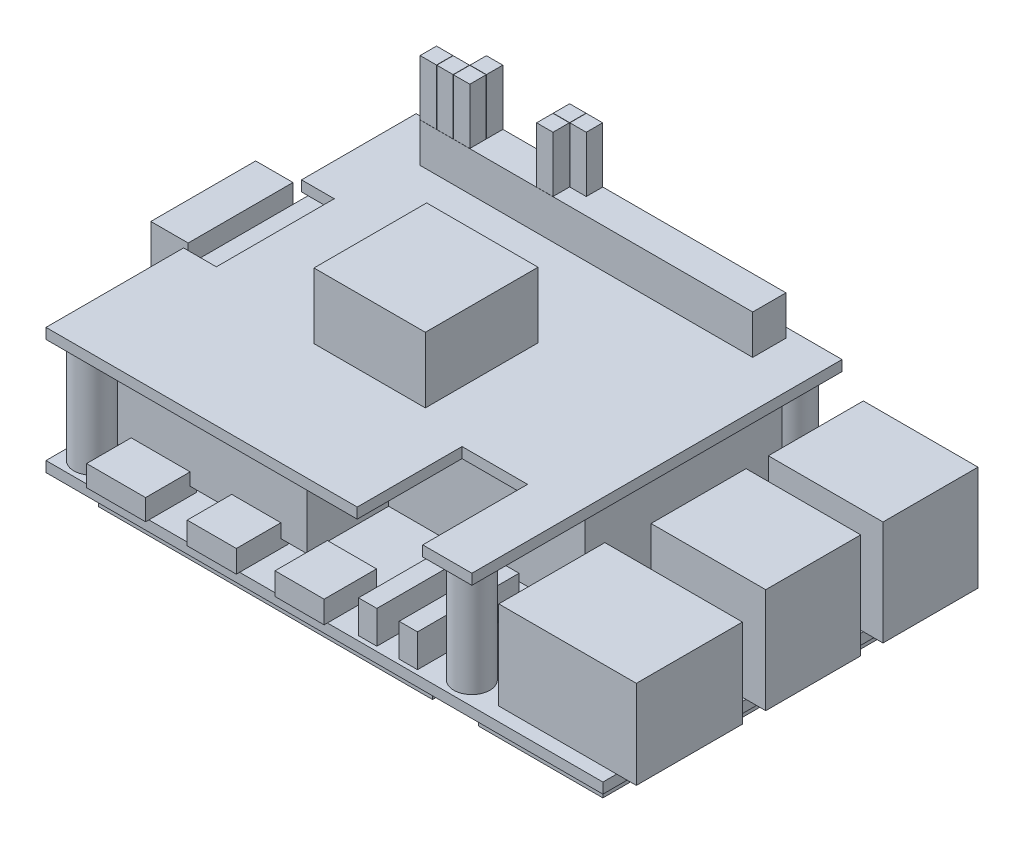
SolidWorks part; units mm, degrees
ref_plane "Front Plane" through (0, 0, 0) normal (0, 0, 1) x (1, 0, 0)
ref_plane "Top Plane" through (0, 0, 0) normal (0, 1, 0) x (1, 0, 0)
ref_plane "Right Plane" through (0, 0, 0) normal (1, 0, 0) x (0, 0, -1)
ref_plane "PZm16" through (0, -16, 0) normal (0, 1, 0) x (1, 0, 0)
sketch "Sketch1" plane through (0, -16, 0) normal (0, 1, 0) x (1, 0, 0)
  line L0 (-55, -92.5) -> (30, -92.5)
  line L1 (30, -92.5) -> (30, -36.5)
  line L2 (30, -36.5) -> (-55, -36.5)
  line L3 (-55, -36.5) -> (-55, -92.5)
extrude "Pi 5 PCB" add sketch "Sketch1" along normal blind 1.6
ref_plane "PZm17_5" through (0, -17.5, 0) normal (0, 1, 0) x (1, 0, 0)
sketch "Sketch2" plane through (0, -17.5, 0) normal (0, 1, 0) x (1, 0, 0)
  line L0 (-48, -91.5) -> (3, -91.5)
  line L1 (3, -91.5) -> (3, -37.5)
  line L2 (3, -37.5) -> (-48, -37.5)
  line L3 (-48, -37.5) -> (-48, -91.5)
extrude "Underside Parts 1" add sketch "Sketch2" along normal blind 1.5
sketch "Sketch3" plane through (0, -17.5, 0) normal (0, 1, 0) x (1, 0, 0)
  line L0 (-54, -85.5) -> (29, -85.5)
  line L1 (29, -85.5) -> (29, -43.5)
  line L2 (29, -43.5) -> (-54, -43.5)
  line L3 (-54, -43.5) -> (-54, -85.5)
extrude "Underside Parts 2" add sketch "Sketch3" along normal blind 1.5
sketch "Sketch4" plane through (0, -17.5, 0) normal (0, 1, 0) x (1, 0, 0)
  line L0 (10, -91.5) -> (29, -91.5)
  line L1 (29, -91.5) -> (29, -37.5)
  line L2 (29, -37.5) -> (10, -37.5)
  line L3 (10, -37.5) -> (10, -91.5)
extrude "Underside Parts 3" add sketch "Sketch4" along normal blind 1.5
sketch "Sketch5" plane through (0, -17.5, 0) normal (0, 1, 0) x (1, 0, 0)
  line L0 (-57.5, -70.5) -> (-41, -70.5)
  line L1 (-41, -70.5) -> (-41, -58.5)
  line L2 (-41, -58.5) -> (-57.5, -58.5)
  line L3 (-57.5, -58.5) -> (-57.5, -70.5)
extrude "microSD Card" add sketch "Sketch5" along normal blind 1.5
ref_plane "PZm13_1" through (0, -13.1, 0) normal (0, 1, 0) x (1, 0, 0)
sketch "Sketch6" plane through (0, -13.1, 0) normal (0, 1, 0) x (1, 0, 0)
  line L0 (-55, -86.2) -> (-21.5, -86.2)
  line L1 (-21.5, -86.2) -> (-21.5, -43.7)
  line L2 (-21.5, -43.7) -> (-55, -43.7)
  line L3 (-55, -43.7) -> (-55, -86.2)
extrude "Cooler Fins" add sketch "Sketch6" along normal blind 13.7
sketch "Sketch7" plane through (0, -13.1, 0) normal (0, 1, 0) x (1, 0, 0)
  line L0 (-21.5, -73.7) -> (8.5, -73.7)
  line L1 (8.5, -73.7) -> (8.5, -43.7)
  line L2 (8.5, -43.7) -> (-21.5, -43.7)
  line L3 (-21.5, -43.7) -> (-21.5, -73.7)
extrude "Cooler Fan" add sketch "Sketch7" along normal blind 13.7
ref_plane "PZm14_4" through (0, -14.4, 0) normal (0, 1, 0) x (1, 0, 0)
sketch "Sketch8" plane through (0, -14.4, 0) normal (0, 1, 0) x (1, 0, 0)
  line L0 (-47.9, -42.54) -> (2.9, -42.54)
  line L1 (2.9, -42.54) -> (2.9, -37.46)
  line L2 (2.9, -37.46) -> (-47.9, -37.46)
  line L3 (-47.9, -37.46) -> (-47.9, -42.54)
extrude "40-pin Header And Stacking Socket" add sketch "Sketch8" along normal blind 16
sketch "Sketch9" plane through (0, -14.4, 0) normal (0, 1, 0) x (1, 0, 0)
  circle A0 centre (-51.5, -89) radius 2.75
extrude "HAT Spacer 1" add sketch "Sketch9" along normal blind 16
sketch "Sketch10" plane through (0, -14.4, 0) normal (0, 1, 0) x (1, 0, 0)
  circle A0 centre (6.5, -89) radius 2.75
extrude "HAT Spacer 2" add sketch "Sketch10" along normal blind 16
sketch "Sketch11" plane through (0, -14.4, 0) normal (0, 1, 0) x (1, 0, 0)
  circle A0 centre (-51.5, -40) radius 2.75
extrude "HAT Spacer 3" add sketch "Sketch11" along normal blind 16
sketch "Sketch12" plane through (0, -14.4, 0) normal (0, 1, 0) x (1, 0, 0)
  circle A0 centre (6.5, -40) radius 2.75
extrude "HAT Spacer 4" add sketch "Sketch12" along normal blind 16
ref_plane "PZ1_6" through (0, 1.6, 0) normal (0, 1, 0) x (1, 0, 0)
sketch "Sketch13" plane through (0, 1.6, 0) normal (0, 1, 0) x (1, 0, 0)
  line L0 (-55, -92.5) -> (-7.5, -92.5)
  line L1 (-7.5, -92.5) -> (-7.5, -76.5)
  line L2 (-7.5, -76.5) -> (2.5, -76.5)
  line L3 (2.5, -76.5) -> (2.5, -92.5)
  line L4 (2.5, -92.5) -> (10, -92.5)
  line L5 (10, -92.5) -> (10, -36)
  line L6 (10, -36) -> (-55, -36)
  line L7 (-55, -36) -> (-55, -53.5)
  line L8 (-55, -53.5) -> (-50, -53.5)
  line L9 (-50, -53.5) -> (-50, -71.5)
  line L10 (-50, -71.5) -> (-55, -71.5)
  line L11 (-55, -71.5) -> (-55, -92.5)
extrude "AI HAT+ PCB" add sketch "Sketch13" along normal blind 1.6
ref_plane "PZ3_2" through (0, 3.2, 0) normal (0, 1, 0) x (1, 0, 0)
sketch "Sketch14" plane through (0, 3.2, 0) normal (0, 1, 0) x (1, 0, 0)
  line L0 (-32.4, -74.2) -> (-15.4, -74.2)
  line L1 (-15.4, -74.2) -> (-15.4, -57)
  line L2 (-15.4, -57) -> (-32.4, -57)
  line L3 (-32.4, -57) -> (-32.4, -74.2)
extrude "Hailo And Heatsink" add sketch "Sketch14" along normal blind 10
sketch "Sketch15" plane through (0, 3.2, 0) normal (0, 1, 0) x (1, 0, 0)
  line L0 (-47.9, -42.54) -> (2.9, -42.54)
  line L1 (2.9, -42.54) -> (2.9, -37.46)
  line L2 (2.9, -37.46) -> (-47.9, -37.46)
  line L3 (-47.9, -37.46) -> (-47.9, -42.54)
extrude "Stacking Pins" add sketch "Sketch15" along normal blind 6
ref_plane "PZ3_7" through (0, 3.7, 0) normal (0, 1, 0) x (1, 0, 0)
sketch "Sketch16" plane through (0, 3.7, 0) normal (0, 1, 0) x (1, 0, 0)
  line L0 (-47.88, -42.52) -> (-45.38, -42.52)
  line L1 (-45.38, -42.52) -> (-45.38, -40.02)
  line L2 (-45.38, -40.02) -> (-47.88, -40.02)
  line L3 (-47.88, -40.02) -> (-47.88, -42.52)
  line L4 (-45.34, -42.52) -> (-42.84, -42.52)
  line L5 (-42.84, -42.52) -> (-42.84, -40.02)
  line L6 (-42.84, -40.02) -> (-45.34, -40.02)
  line L7 (-45.34, -40.02) -> (-45.34, -42.52)
  line L8 (-42.8, -42.52) -> (-40.3, -42.52)
  line L9 (-40.3, -42.52) -> (-40.3, -40.02)
  line L10 (-40.3, -40.02) -> (-42.8, -40.02)
  line L11 (-42.8, -40.02) -> (-42.8, -42.52)
  line L12 (-42.8, -39.98) -> (-40.3, -39.98)
  line L13 (-40.3, -39.98) -> (-40.3, -37.48)
  line L14 (-40.3, -37.48) -> (-42.8, -37.48)
  line L15 (-42.8, -37.48) -> (-42.8, -39.98)
  line L16 (-30.1, -42.52) -> (-27.6, -42.52)
  line L17 (-27.6, -42.52) -> (-27.6, -40.02)
  line L18 (-27.6, -40.02) -> (-30.1, -40.02)
  line L19 (-30.1, -40.02) -> (-30.1, -42.52)
  line L20 (-30.1, -39.98) -> (-27.6, -39.98)
  line L21 (-27.6, -39.98) -> (-27.6, -37.48)
  line L22 (-27.6, -37.48) -> (-30.1, -37.48)
  line L23 (-30.1, -37.48) -> (-30.1, -39.98)
  line L24 (-27.56, -39.98) -> (-25.06, -39.98)
  line L25 (-25.06, -39.98) -> (-25.06, -37.48)
  line L26 (-25.06, -37.48) -> (-27.56, -37.48)
  line L27 (-27.56, -37.48) -> (-27.56, -39.98)
extrude "Dupont Housings" add sketch "Sketch16" along normal blind 14
ref_plane "PZm15_4" through (0, -15.4, 0) normal (0, 1, 0) x (1, 0, 0)
sketch "Sketch17" plane through (0, -15.4, 0) normal (0, 1, 0) x (1, 0, 0)
  line L0 (-61, -70.5) -> (-55.3, -70.5)
  line L1 (-55.3, -70.5) -> (-55.3, -54.5)
  line L2 (-55.3, -54.5) -> (-61, -54.5)
  line L3 (-61, -54.5) -> (-61, -70.5)
extrude "PCIe Flat Cable Loop" add sketch "Sketch17" along normal blind 18.6
sketch "Sketch18" plane through (0, -14.4, 0) normal (0, 1, 0) x (1, 0, 0)
  line L0 (12, -90.4) -> (33, -90.4)
  line L1 (33, -90.4) -> (33, -74.2)
  line L2 (33, -74.2) -> (12, -74.2)
  line L3 (12, -74.2) -> (12, -90.4)
extrude "Ethernet" add sketch "Sketch18" along normal blind 13.5
sketch "Sketch19" plane through (0, -14.4, 0) normal (0, 1, 0) x (1, 0, 0)
  line L0 (15.5, -70.65) -> (33, -70.65)
  line L1 (33, -70.65) -> (33, -56.15)
  line L2 (33, -56.15) -> (15.5, -56.15)
  line L3 (15.5, -56.15) -> (15.5, -70.65)
  line L4 (15.5, -52.75) -> (33, -52.75)
  line L5 (33, -52.75) -> (33, -38.25)
  line L6 (33, -38.25) -> (15.5, -38.25)
  line L7 (15.5, -38.25) -> (15.5, -52.75)
extrude "USB-A Stacks" add sketch "Sketch19" along normal blind 16
sketch "Sketch20" plane through (0, -14.4, 0) normal (0, 1, 0) x (1, 0, 0)
  line L0 (-48.3, -93) -> (-39.3, -93)
  line L1 (-39.3, -93) -> (-39.3, -85.2)
  line L2 (-39.3, -85.2) -> (-48.3, -85.2)
  line L3 (-48.3, -85.2) -> (-48.3, -93)
extrude "USB-C" add sketch "Sketch20" along normal blind 3.2
sketch "Sketch21" plane through (0, -14.4, 0) normal (0, 1, 0) x (1, 0, 0)
  line L0 (-32.95, -93) -> (-25.45, -93)
  line L1 (-25.45, -93) -> (-25.45, -85)
  line L2 (-25.45, -85) -> (-32.95, -85)
  line L3 (-32.95, -85) -> (-32.95, -93)
  line L4 (-19.55, -93) -> (-12.05, -93)
  line L5 (-12.05, -93) -> (-12.05, -85)
  line L6 (-12.05, -85) -> (-19.55, -85)
  line L7 (-19.55, -85) -> (-19.55, -93)
extrude "Micro-HDMI" add sketch "Sketch21" along normal blind 3.4
sketch "Sketch22" plane through (0, -14.4, 0) normal (0, 1, 0) x (1, 0, 0)
  line L0 (-8, -91.8) -> (-5.2, -91.8)
  line L1 (-5.2, -91.8) -> (-5.2, -76.3)
  line L2 (-5.2, -76.3) -> (-8, -76.3)
  line L3 (-8, -76.3) -> (-8, -91.8)
  line L4 (-1.8, -91.8) -> (1, -91.8)
  line L5 (1, -91.8) -> (1, -76.3)
  line L6 (1, -76.3) -> (-1.8, -76.3)
  line L7 (-1.8, -76.3) -> (-1.8, -91.8)
extrude "CAM-DISP Connectors" add sketch "Sketch22" along normal blind 5
